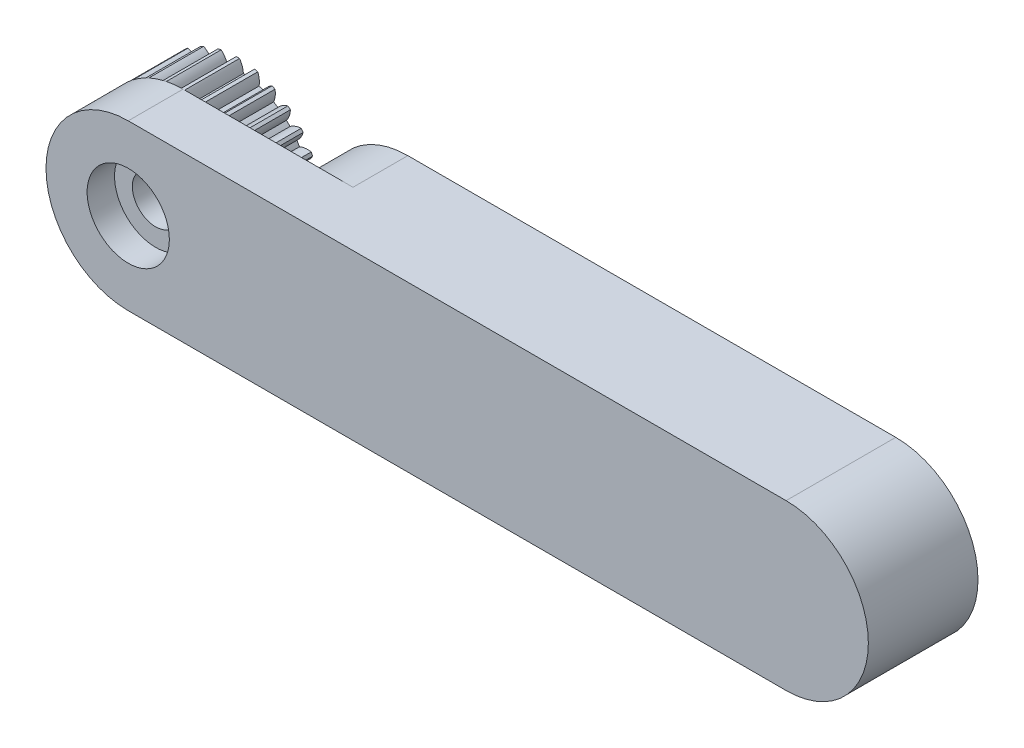
SolidWorks part; units mm, degrees
note: The reader was unsure of these and kept them because the rebuilt part matched: shared geometry of "Sketch2<3>", "Sketch6<3>".
ref_plane "Front Plane" through (0, 0, 0) normal (0, 0, 1) x (1, 0, 0)
ref_plane "Top Plane" through (0, 0, 0) normal (0, 1, 0) x (1, 0, 0)
ref_plane "Right Plane" through (0, 0, 0) normal (1, 0, 0) x (0, 0, -1)
sketch "Sketch2" plane through (0, 0, 0) normal (0, 0, 1) x (1, 0, 0)
  line L0 (0, 0) -> (0, 18.136) construction
  line L1 (0.3, 15) -> (-0.3, 15)
  circle A0 centre (0, 0) radius 13
  circle A1 centre (0, 0) radius 4.25
  circle A2 centre (0, 0) radius 15 construction
  arc A3 (-0.3, 15) -> (-1, 12.9615) centre (2.738, 12.8174) ccw
  arc A4 (0.3, 15) -> (1, 12.9615) centre (-2.738, 12.8174) cw
  point P11 (-0.8, 14.0322)
  point P13 (0, 15)
  dimension "D1" = 26
  dimension "D2" = 8.5
  dimension "D6" = 0.8
  dimension "D7" = 30
  dimension "D4" = 0.6
  dimension "D5" = 1
  dimension "D3" = 2
extrude "Boss-Extrude1" add sketch "Sketch2" along normal blind 10 contours A0 A1
extrude "Boss-Extrude2" add sketch "Sketch2<3>" along normal blind 10 contours A4 L1 A3 A0
sketch "Sketch2<3>" plane through (0, 0, 0) normal (0, 0, 1) x (1, 0, 0) same geometry as "Sketch2"
pattern_circular "CirPattern1" count 28 over 360 about axis through (0, 0, 0) along (0, 0, 1) of "Boss-Extrude2"
sketch "Sketch3" plane through (0, 0, 10) normal (0, 0, 1) x (1, 0, 0)
  circle A0 centre (0, 0) radius 15
  circle A1 centre (0, 0) radius 7.5
  dimension "D1" = 30
  dimension "D2" = 15
extrude "Boss-Extrude3" add sketch "Sketch3" along normal blind 10
sketch "Sketch5" plane through (0, 0, 10) normal (0, 0, 1) x (1, 0, 0)
  circle A0 centre (0, 0) radius 4.25
  circle A1 centre (0, 0) radius 7.5
extrude "Boss-Extrude4" add sketch "Sketch5" along normal blind 5
sketch "Sketch6" plane through (0, 0, 20) normal (0, 0, 1) x (1, 0, 0)
  line L0 (0, 0) -> (120, 0) construction
  line L1 (0, 15) -> (120, 15)
  line L2 (0, -15) -> (120, -15)
  line L3 (16, 15) -> (16, -15)
  circle A0 centre (120, 0) radius 15
  circle A1 centre (0, 0) radius 15 construction
  arc A2 (0, 15) -> (0, -15) centre (0, 0) cw
  dimension "D2" = 16
  dimension "D1" = 120
extrude "Boss-Extrude5" add sketch "Sketch6" against normal blind 20 separate body
extrude "Boss-Extrude6" add sketch "Sketch6<3>" against normal blind 10
sketch "Sketch6<3>" plane through (0, 0, 20) normal (0, 0, 1) x (1, 0, 0) same geometry as "Sketch6"
fillet "Fillet1" radius 15 2 edges at (16, 15, 5) (16, -15, 5)
